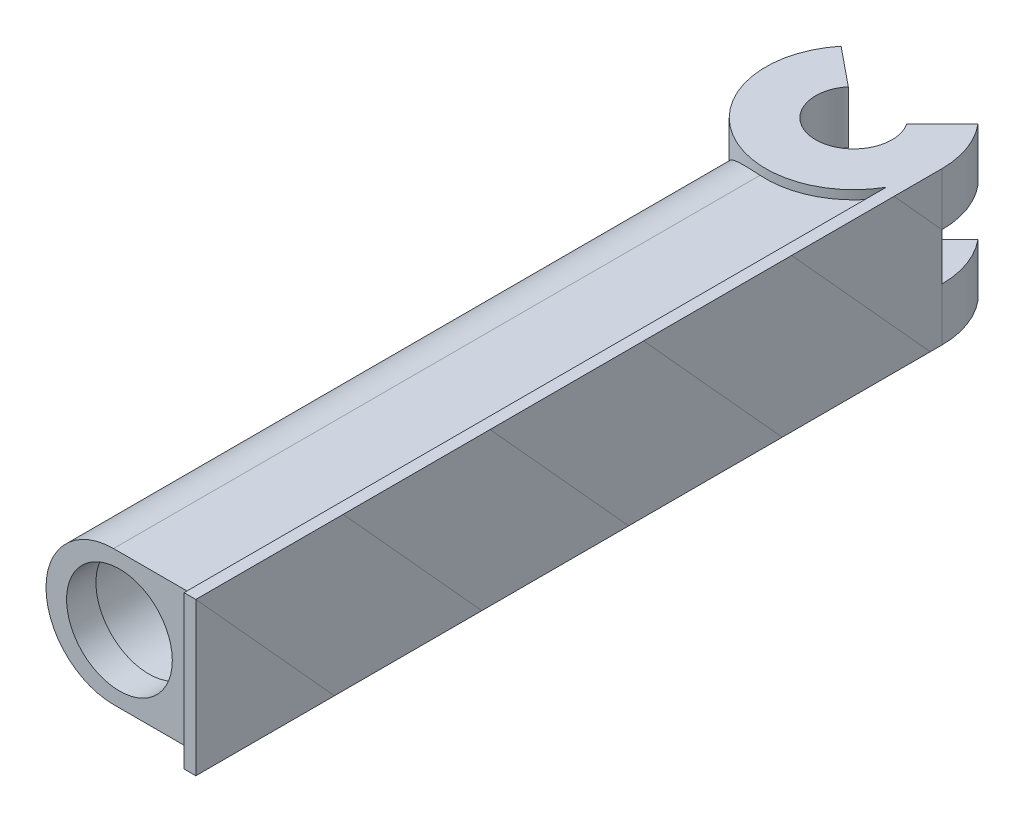
SolidWorks part; units mm, degrees
ref_plane "Front Plane" through (0, 0, 0) normal (0, 0, 1) x (1, 0, 0)
ref_plane "Top Plane" through (0, 0, 0) normal (0, 1, 0) x (1, 0, 0)
ref_plane "Right Plane" through (0, 0, 0) normal (1, 0, 0) x (0, 0, -1)
sketch "Sketch1" plane through (0, 0, 0) normal (0, 1, 0) x (1, 0, 0)
  circle A0 centre (0, 0) radius 30
  dimension "D1" = 60
extrude "Boss-Extrude1" add sketch "Sketch1" along normal mid plane 52
sketch "Sketch2" plane through (0, 0, 0) normal (0, 0, 1) x (1, 0, 0)
  line L0 (30, 26) -> (30, -26)
  line L1 (30, -26) -> (26, -26)
  line L2 (26, -26) -> (26, -23)
  line L3 (26, -23) -> (-2, -23)
  line L4 (-2, 23) -> (26, 23)
  line L5 (26, 23) -> (26, 26)
  line L6 (30, 26) -> (-30, 26) construction
  line L7 (26, 26) -> (30, 26)
  arc A0 (-2, -23) -> (-2, 23) centre (-2, 0) cw
  dimension "D1" = 3
  dimension "D2" = 4
  dimension "D3" = 28
extrude "Boss-Extrude2" add sketch "Sketch2" along normal blind 250
sketch "Sketch3" plane through (0, 0, 0) normal (0, 1, 0) x (1, 0, 0)
  circle A0 centre (0, 0) radius 13
  dimension "D1" = 26
extrude "Cut-Extrude1" cut sketch "Sketch3" against normal mid plane 52
extrude "Cut-Extrude2" cut sketch "Sketch1<2>" against normal mid plane 16
sketch "Sketch1<2>" plane through (0, 0, 0) normal (0, 1, 0) x (1, 0, 0) same geometry as "Sketch1"
sketch "Sketch4" plane through (0, 0, 250) normal (0, 0, 1) x (1, 0, 0)
  circle A0 centre (0, 0) radius 19
  dimension "D1" = 38
extrude "Cut-Extrude3" cut sketch "Sketch4" against normal blind 210
sketch "Sketch6" plane through (0, 0, 250) normal (0, 0, 1) x (1, 0, 0)
  circle A0 centre (0, 0) radius 18
  circle M2 centre (0, 0) radius 19
  dimension "D1" = 36
extrude "Boss-Extrude3" add sketch "Sketch6" against normal blind 10 contours A0 M2 region at (-18.4626, 0, 250)
sketch "Sketch7" plane through (0, 0, 0) normal (0, 1, 0) x (1, 0, 0)
  line L1 (26, -250) -> (30, -250)
  line L2 (26, -250) -> (26, -254)
  line L3 (26, -254) -> (30, -254)
  line L4 (30, -250) -> (30, -254)
  dimension "D1" = 4
extrude "Boss-Extrude4" add sketch "Sketch7" along normal mid plane 52
sketch "Sketch8" plane through (30, 0, 0) normal (1, 0, 0) x (0, 0, -1)
  line L0 (-254, 26) -> (-206.8001, -26)
  line L1 (-203.8332, 26) -> (-156.6332, -26)
  line L2 (-153.8332, 26) -> (-106.6332, -26)
  line L3 (-101.5753, 26) -> (-54.3753, -26)
  line L4 (-51.1795, 26) -> (-3.9795, -26)
  line L5 (-16.3384, 26) -> (0, 8)
  line L6 (-254, -26) -> (0, -26) construction
  line L7 (-254, 26) -> (0, 26) construction
  line L8 (-254, 26) -> (-254, -26) construction
split line "Split Line1"
ref_plane "Plane1" through (-35, 0, 0) normal (1, 0, 0) x (0, 0, -1)
sketch "Sketch9" plane through (0, 26, 0) normal (0, 1, 0) x (1, 0, 0)
  line L0 (-23.2736, 18.9298) -> (-10.0852, 8.2029)
  line L1 (10.8351, 7.1834) -> (22.9603, 19.3086)
  line L8 (26, -14.9666) -> (26, -254)
  line L9 (26, -254) -> (30, -254)
  line L10 (30, -254) -> (30, -203.8332)
  line L11 (30, -203.8332) -> (30, -153.8332)
  line L12 (30, -153.8332) -> (30, -101.5753)
  line L13 (30, -101.5753) -> (30, -51.1795)
  line L14 (30, -51.1795) -> (30, -16.3384)
  line L15 (30, -16.3384) -> (30, 0)
  line L17 (26, -254) -> (30, -254)
  line L18 (30, -254) -> (30, -203.8332)
  line L19 (30, -203.8332) -> (30, -153.8332)
  line L20 (30, -153.8332) -> (30, -101.5753)
  arc A1 (30, 0) -> (26, -14.9666) centre (0, 0) ccw
  arc A2 (22.9603, 19.3086) -> (-23.2736, 18.9298) centre (0, 0) ccw
  circle A3 centre (0, 0) radius 13 construction
  arc A4 (10.8351, 7.1834) -> (-10.0852, 8.2029) centre (0, 0) ccw
  dimension "D1" = 0
extrude "Cut-Extrude4" cut sketch "Sketch9" against normal up to surface (52 mm away) contours A4 L0 A2 L1 up to face at (0, -26, 13)
